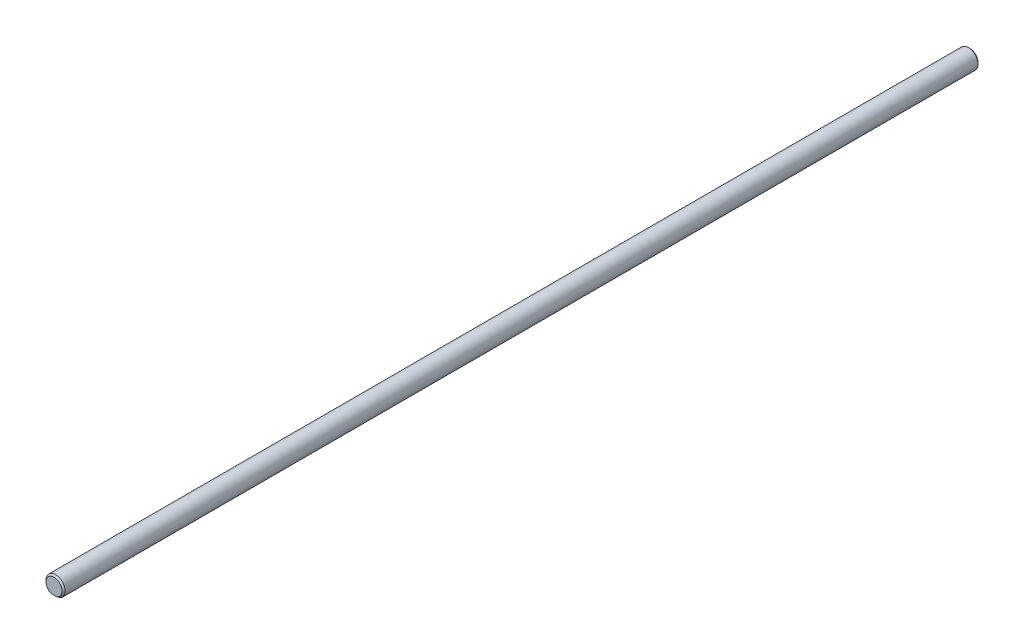
SolidWorks part; units mm, degrees
ref_plane "Front" through (0, 0, 0) normal (0, 0, 1) x (1, 0, 0)
ref_plane "Top" through (0, 0, 0) normal (0, 1, 0) x (1, 0, 0)
ref_plane "Right" through (0, 0, 0) normal (1, 0, 0) x (0, 0, -1)
sketch "Sketch1" plane through (0, 0, 0) normal (0, 0, 1) x (1, 0, 0)
  line L0 (-1.905, -2.54) -> (1.905, -2.54)
  circle A0 centre (0, 0) radius 3.175 construction
  arc A1 (-1.905, -2.54) -> (1.905, -2.54) centre (0, 0) cw
  dimension "D1" = 6.35
  dimension "D2" = 5.715
sketch "Sketch2" plane through (0, 0, 0) normal (0, 1, 0) x (1, 0, 0)
  line L0 (0, -152.4) -> (0, 152.4)
  point P3 (0, 0)
  dimension "D1" = 304.8
sweep "Sweep1" add profiles "Sketch1" path "Sketch2"
chamfer "Chamfer1" distance 0.5 angle 45 2 edges at (0, 3.175, -152.4) (0, 3.175, 152.4)
ref_axis "Axis1" through (0, 0, -151.9) along (0, 0, 1)
